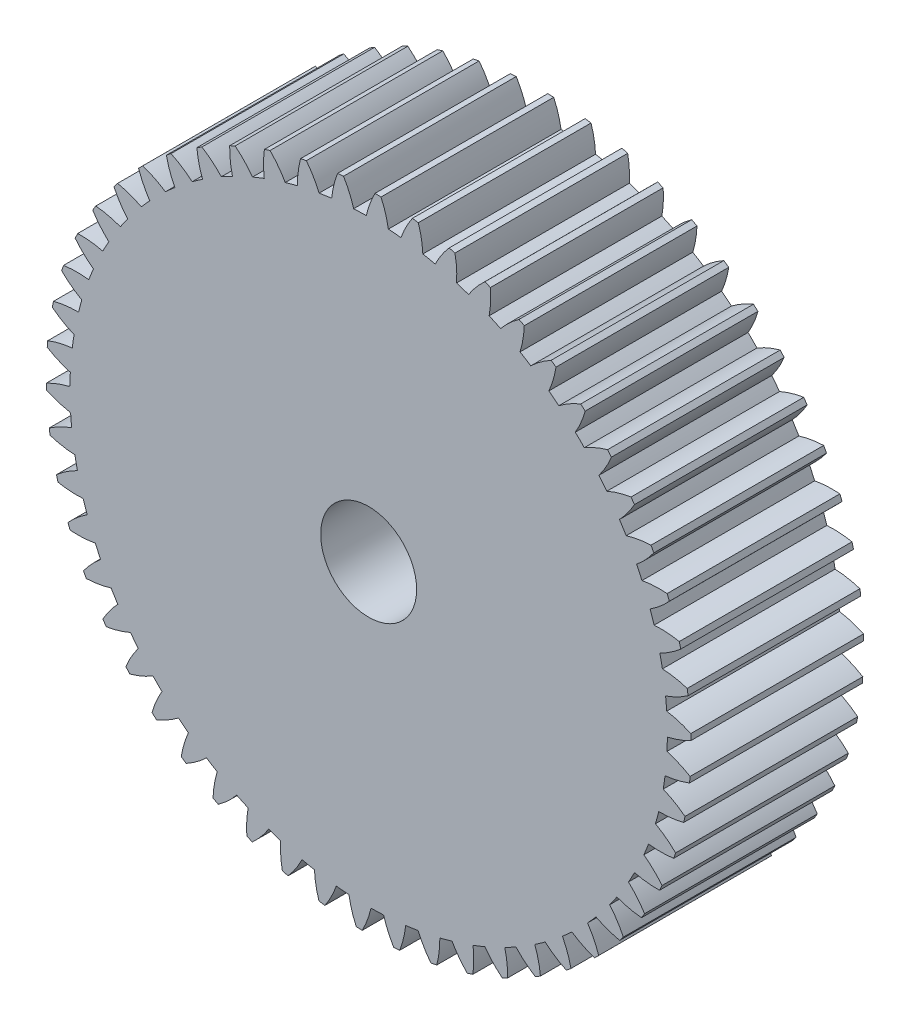
SolidWorks part; units mm, degrees
ref_plane "Front Plane" through (0, 0, 0) normal (0, 0, 1) x (1, 0, 0)
ref_plane "Top Plane" through (0, 0, 0) normal (0, 1, 0) x (1, 0, 0)
ref_plane "Right Plane" through (0, 0, 0) normal (1, 0, 0) x (0, 0, -1)
sketch "Sketch2" plane through (0, 0, 0) normal (0, 0, 1) x (1, 0, 0)
  line L0 (-81, 0) -> (-81, 24.0946)
  line L1 (-81, 0) -> (-71.5388, 25.9945)
  line L2 (-76.1151, 0) -> (-84, 0) construction
  line L3 (-76.1151, 0) -> (-80.0576, 0)
  line L4 (-80.0576, 0) -> (-84, 0)
  line L5 (-80.0576, 0) -> (-72.3668, -23.5914) construction
  line L6 (-80.0576, 0) -> (-77.494, -7.8638)
  line L7 (-77.494, -7.8638) -> (-74.9304, -15.7276)
  line L8 (-74.9304, -15.7276) -> (-72.3668, -23.5914)
  line L9 (-72.3668, -23.5914) -> (-69.8032, -31.4552)
  line L10 (0, 0) -> (-83.9645, -2.4431) construction
  line L11 (0, 0) -> (-80.0576, 0) construction
  circle A0 centre (0, 0) radius 81
  circle A1 centre (0, 0) radius 77.8255
  circle A2 centre (0, 0) radius 84
  circle A3 centre (0, 0) radius 76.1151
  arc A4 (-83.9835, -1.6653) -> (-77.823, 0.6146) centre (-72.3668, -23.5914) cw
  arc A5 (-83.9382, -3.2207) -> (-77.6556, -5.1386) centre (-73.6161, 19.3438) ccw
  dimension "D1" = 162
  dimension "D2" = 168
  dimension "D3" = 155.6509
  dimension "D4" = 20
  dimension "D6" = 1.667
sketch "Sketch5" plane through (0, 0, 0) normal (0, 0, 1) x (1, 0, 0)
  arc A0 (-77.823, 0.6146) -> (-83.9835, -1.6653) centre (-72.3668, -23.5914) ccw construction
  arc A1 (-77.823, 0.6146) -> (-83.9835, -1.6653) centre (-72.3668, -23.5914) ccw
  arc A2 (-83.9382, -3.2207) -> (-77.6556, -5.1386) centre (-73.6161, 19.3438) ccw construction
  arc A3 (-83.9382, -3.2207) -> (-77.6556, -5.1386) centre (-73.6161, 19.3438) ccw
  circle A4 centre (0, 0) radius 77.8255 construction
  circle A5 centre (0, 0) radius 84 construction
  arc A6 (-77.823, 0.6146) -> (-77.6556, -5.1386) centre (0, 0) ccw
  arc A7 (-83.9835, -1.6653) -> (-83.9382, -3.2207) centre (0, 0) ccw
extrude "Boss-Extrude3" add sketch "Sketch5" along normal blind 45
extrude "Boss-Extrude4" add sketch "Sketch2" along normal blind 45 contours A1
fillet "Fillet1" radius 0.5 1 edges at (-77.823, 0.6146, 22.5)
fillet "Fillet3" radius 0.5 1 edges at (-77.6556, -5.1386, 22.5)
sketch "Sketch6" plane through (0, 0, 45) normal (0, 0, 1) x (1, 0, 0)
  circle A0 centre (0, 0) radius 12.5
  dimension "D1" = 25
pattern_circular "CirPattern1" count 54 over 360 about axis through (0, 0, 45) along (0, 0, -1) of "Boss-Extrude3"
extrude "Cut-Extrude1" cut sketch "Sketch6" against normal blind 45
equation "\"Teeth\" = 54"
equation "\"Module\"= 3"
equation "\"pcd\"= \"Teeth\" * \"Module\""
equation "\"circularpitch\"= 3.1415 * \"Module\""
equation "\"diametricalpitch\"= 1 / \"Module\""
equation "\"addendum\"= \"Module\""
equation "\"addendumCircularDiameter\"= \"pcd\" + 2 * \"Module\""
equation "\"clearance\"= \"circularpitch\" / \"Teeth\""
equation "\"dedendum\"= \"addendum\" + \"clearance\""
equation "\"dedendumCircularDiameter\"= \"pcd\" - 2 * \"dedendum\""
equation "\"pressureangle\"= 20"
equation "\"circularpitchangle\"= \"circularpitch\" * 360 / ( 3.1415 * \"pcd\" * 4 )"
equation "\"D2@Sketch2\"=\"addendumCircularDiameter\""
equation "\"D1@Sketch2\"=\"pcd\""
equation "\"D3@Sketch2\"=\"dedendumCircularDiameter\""
equation "\"D4@Sketch2\"=\"pressureangle\""
equation "\"D6@Sketch2\"=\"circularpitchangle\""
equation "\"D1@CirPattern1\"=\"Teeth\""
